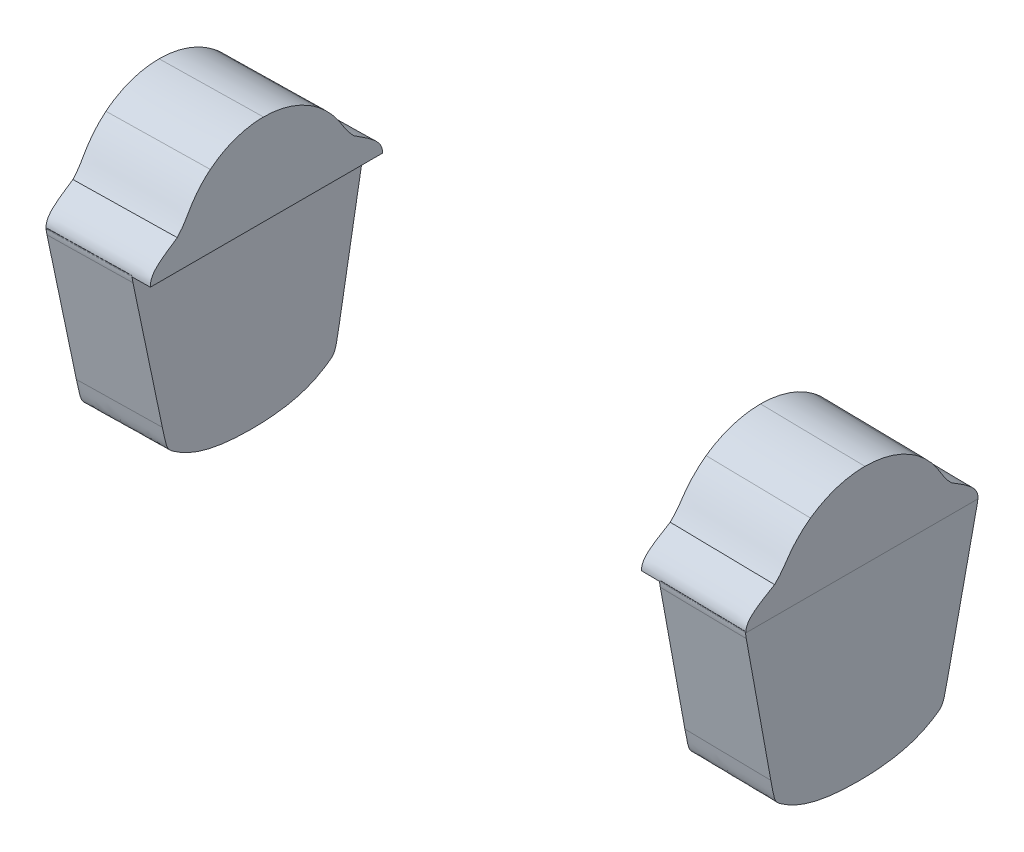
SolidWorks part; units mm, degrees
ref_plane "Front Plane" through (0, 0, 0) normal (0, 0, 1) x (1, 0, 0)
ref_plane "Top Plane" through (0, 0, 0) normal (0, 1, 0) x (1, 0, 0)
ref_plane "Right Plane" through (0, 0, 0) normal (1, 0, 0) x (0, 0, -1)
sketch "Sketch13" plane through (-330.9386, -5.7766, 0) normal (0.9998, 0.0175, 0) x (0, 0, -1)
  line L3 (82.505, 100.855) -> (104.453, 212.7636)
  line L4 (105.1118, 218.0433) -> (-84.0339, 218.0433)
  line L5 (-83.375, 212.7636) -> (-61.427, 100.855)
  line L6 (82.505, 100.855) -> (104.453, 212.7636)
  line L7 (105.1118, 218.0433) -> (-84.0339, 218.0433)
  line L8 (-83.375, 212.7636) -> (-61.427, 100.855)
  spline S6 degree 3 poles (7626.2022, 16335.3726) (93.3065, 1190.3174) (-262.8295, 156.049) (-31.4208, 69.2057) (-26.7523, 67.9017) (-16.9505, 65.8726) (-11.819, 65.149) (405.2965, 28.3291) (2318.1729, 1443.9996) (16961.578, -5460.1262) knots -12.504091 -12.504091 -12.504091 -12.504091 0.25 0.25 0.5 0.5 0.75 0.75 19.845941 19.845941 19.845941 19.845941 weights 1 1 1 1 1 1 1 1 1 1 only from (-48.4941, 77.0769) to (10.539, 63.9704)
  spline S7 degree 3 poles (-16940.096, -5459.9357) (-2297.0598, 1443.9736) (-384.2148, 28.3294) (32.8969, 65.149) (38.0285, 65.8726) (47.8302, 67.9017) (52.4988, 69.2057) (283.9075, 156.049) (-72.2286, 1190.3176) (-7605.1261, 16335.3764) knots -18.845765 -18.845765 -18.845765 -18.845765 0.25 0.25 0.5 0.5 0.75 0.75 13.504092 13.504092 13.504092 13.504092 weights 1 1 1 1 1 1 1 1 1 1 only from (10.539, 63.9704) to (69.5721, 77.0769)
  spline S8 degree 3 poles (-8963.5548, -15472.3763) (-752.2665, -318.1531) (7.9888, 36.6232) (73.8797, 79.8406) (74.6824, 80.3989) (76.0321, 81.4603) (76.5773, 81.961) (77.5011, 82.9989) (77.8915, 83.5469) (78.431, 84.5204) (78.6051, 84.8746) (78.9428, 85.6519) (79.1069, 86.0756) (79.5941, 87.4807) (79.9091, 88.59) (101.7921, 178.014) (164.8063, 1219.1751) (7787.4412, 16356.1941) knots -8.34761 -8.34761 -8.34761 -8.34761 0.125 0.125 0.25 0.25 0.375 0.375 0.5 0.5 0.5625 0.5625 0.625 0.625 0.75 0.75 9.036838 9.036838 9.036838 9.036838 weights 1 1 1 1 1 1 1 1 1 1 1 1 1 1 1 1 1 1 only from (69.5721, 77.0769) to (82.505, 100.855)
  spline S9 degree 3 poles (8221.7045, -15798.6868) (-629.2195, -357.5895) (98.26, 120.5911) (112.1266, 316.5514) (-660.8382, 12.0074) (-15219.7335, 9632.9671) knots -9.423347 -9.423347 -9.423347 -9.423347 0.125 0.125 10.033525 10.033525 10.033525 10.033525 weights 1 1 1 1 1 1 only from (104.453, 212.7636) to (105.1118, 218.0433)
  spline S10 degree 3 poles (15241.4841, 9633.4116) (681.9399, 11.998) (-91.0488, 316.5529) (-77.1822, 120.5925) (650.2762, -357.5756) (-8200.2406, -15798.0135) knots -9.86503 -9.86503 -9.86503 -9.86503 0.043648 0.043648 9.591856 9.591856 9.591856 9.591856 weights 1 1 1 1 1 1 only from (-84.0339, 218.0433) to (-83.375, 212.7636)
  spline S11 degree 3 poles (-7766.5357, 16356.5365) (-143.7293, 1219.1908) (-80.7143, 178.0147) (-58.8312, 88.59) (-58.5162, 87.4807) (-58.029, 86.0756) (-57.8649, 85.6519) (-57.5272, 84.8746) (-57.3531, 84.5204) (-56.8136, 83.5469) (-56.4232, 82.9989) (-55.4993, 81.961) (-54.9541, 81.4603) (-53.6044, 80.3989) (-52.8018, 79.8406) (13.0901, 36.6226) (773.3666, -318.1635) (8984.992, -15473.0393) knots -8.036901 -8.036901 -8.036901 -8.036901 0.25 0.25 0.375 0.375 0.4375 0.4375 0.5 0.5 0.625 0.625 0.75 0.75 0.875 0.875 9.347734 9.347734 9.347734 9.347734 weights 1 1 1 1 1 1 1 1 1 1 1 1 1 1 1 1 1 1 only from (-61.427, 100.855) to (-48.4941, 77.0769)
  spline S12 degree 3 poles (-48.4941, 77.0769) (-44.5431, 74.5789) (-40.3184, 72.5447) (-31.4208, 69.2057) (-26.7523, 67.9017) (-16.9505, 65.8726) (-11.819, 65.149) (-1.0385, 64.1973) (4.609, 63.9704) (10.539, 63.9704) knots 0 0 0 0 0.25 0.25 0.5 0.5 0.75 0.75 1 1 1 1 weights 1 1 1 1 1 1 1 1 1 1
  spline S13 degree 3 poles (10.539, 63.9704) (16.469, 63.9704) (22.1165, 64.1973) (32.8969, 65.149) (38.0285, 65.8726) (47.8302, 67.9017) (52.4988, 69.2057) (61.3963, 72.5447) (65.621, 74.5789) (69.5721, 77.0769) knots 0 0 0 0 0.25 0.25 0.5 0.5 0.75 0.75 1 1 1 1 weights 1 1 1 1 1 1 1 1 1 1
  spline S14 degree 3 poles (69.5721, 77.0769) (70.8544, 77.8877) (71.9638, 78.584) (73.8797, 79.8406) (74.6824, 80.3989) (76.0321, 81.4603) (76.5773, 81.961) (77.5011, 82.9989) (77.8915, 83.5469) (78.431, 84.5204) (78.6051, 84.8746) (78.9428, 85.6519) (79.1069, 86.0756) (79.5941, 87.4807) (79.9091, 88.59) (80.8846, 92.5765) (81.5727, 96.1016) (82.505, 100.855) knots 0 0 0 0 0.125 0.125 0.25 0.25 0.375 0.375 0.5 0.5 0.5625 0.5625 0.625 0.625 0.75 0.75 1 1 1 1 weights 1 1 1 1 1 1 1 1 1 1 1 1 1 1 1 1 1 1
  spline S15 degree 3 poles (104.453, 212.7636) (104.7645, 214.1816) (104.9761, 215.5021) (105.0958, 217.1935) (105.1118, 217.6218) (105.1118, 218.0433) knots 0.000354 0.000354 0.000354 0.000354 0.125 0.125 0.168294 0.168294 0.168294 0.168294 weights 1 1 1 1 1 1
  spline S16 degree 3 poles (-84.0339, 218.0433) (-84.0339, 217.6218) (-84.0179, 217.1935) (-83.8982, 215.5021) (-83.6866, 214.1816) (-83.375, 212.7636) knots 0.000354 0.000354 0.000354 0.000354 0.043648 0.043648 0.168294 0.168294 0.168294 0.168294 weights 1 1 1 1 1 1
  spline S17 degree 3 poles (-61.427, 100.855) (-60.4948, 96.1016) (-59.8067, 92.5765) (-58.8312, 88.59) (-58.5162, 87.4807) (-58.029, 86.0756) (-57.8649, 85.6519) (-57.5272, 84.8746) (-57.3531, 84.5204) (-56.8136, 83.5469) (-56.4232, 82.9989) (-55.4993, 81.961) (-54.9541, 81.4603) (-53.6044, 80.3989) (-52.8018, 79.8406) (-50.8858, 78.584) (-49.7765, 77.8877) (-48.4941, 77.0769) knots 0 0 0 0 0.25 0.25 0.375 0.375 0.4375 0.4375 0.5 0.5 0.625 0.625 0.75 0.75 0.875 0.875 1 1 1 1 weights 1 1 1 1 1 1 1 1 1 1 1 1 1 1 1 1 1 1
  dimension "D1" = 0
extrude "Boss-Extrude1" add sketch "Sketch13" along normal blind 70 from offset 50 separate body
sketch "Sketch14" plane through (-277.0872, -9.6761, 0) normal (0.9994, 0.0349, 0) x (0, 0, -1)
  line L1 (-84.0231, 222.0431) -> (105.1011, 222.0431)
  line L2 (-84.0231, 222.0431) -> (105.1011, 222.0431)
  spline S6 degree 2 poles (5382.3297, -4104.2021) (311.5748, 636.7455) (-41.4346, 271.4203) (-45.2753, 267.4456) (-48.46, 262.9662) (-49.2003, 261.9249) (-50.0127, 260.7006) (-50.6823, 259.6915) (-51.5083, 258.3944) (-51.7922, 257.9484) (-52.2439, 257.2325) (-52.8322, 256.3001) (-52.9781, 256.0697) (-53.8513, 254.6905) (-54.4673, 253.7605) (-56.096, 251.3012) (-57.6776, 249.3237) (-297.7474, -50.8443) (-6935.3487, 1483.9527) knots -22.859625 -22.859625 -22.859625 0.25 0.25 0.5 0.5 0.5625 0.5625 0.625 0.625 0.65625 0.65625 0.6875 0.6875 0.75 0.75 0.875 0.875 18.832979 18.832979 18.832979 only from (-33.2448, 278.7269) to (-61.3296, 245.2339)
  spline S7 degree 2 poles (5930.5505, 3863.7565) (57.6161, 320.2206) (-64.9183, 242.9931) (-66.8739, 241.7606) (-68.4807, 240.7123) (-70.427, 239.4425) (-71.9939, 238.3559) (-73.913, 237.0251) (-75.4132, 235.8649) (-77.2608, 234.4361) (-78.6285, 233.1445) (-80.3322, 231.5357) (-81.4458, 229.989) (-82.0893, 229.095) (-82.5638, 228.1868) (-83.064, 227.2294) (-83.3895, 226.2273) (-146.1003, 33.1712) (5997.7888, -3233.0606) knots -10.71994 -10.71994 -10.71994 0.125 0.125 0.25 0.25 0.375 0.375 0.5 0.5 0.625 0.625 0.75 0.75 0.8125 0.8125 0.875 0.875 13.331152 13.331152 13.331152 only from (-61.3296, 245.2339) to (-84.0231, 222.0431)
  spline S8 degree 3 poles (7099.4552, 417.9562) (33.7422, 171.0257) (106.9497, 198.6055) (105.0313, 223.5586) (104.9316, 224.3311) (104.7815, 225.1141) (104.5764, 225.9071) (104.3103, 226.7096) (103.9775, 227.5213) (103.5717, 228.3417) (103.0877, 229.1717) (102.1684, 230.5333) (100.7506, 232.177) (98.9584, 233.8577) (97.5515, 235.0337) (96.1206, 236.1607) (94.4601, 237.3912) (92.307, 238.8932) (90.0075, 240.4269) (87.5759, 241.9971) (-20.5227, 310.2792) (-159.6048, 327.1069) (3459.6832, 6362.2993) knots -2.147809 -2.147809 -2.147809 -2.147809 0.022137 0.044649 0.067605 0.091096 0.115221 0.140113 0.165931 0.19286 0.221122 0.250979 0.338288 0.412598 0.468467 0.500662 0.573936 0.651492 0.733183 0.818756 0.907882 12.058636 12.058636 12.058636 12.058636 only from (105.1011, 222.0431) to (82.4076, 245.2339)
  spline S9 degree 2 poles (6949.7745, 1520.3026) (319.1368, -51.545) (78.7391, 249.3443) (77.1571, 251.3243) (75.524, 253.7924) (74.9106, 254.7196) (74.0342, 256.1042) (73.9122, 256.2968) (73.2996, 257.2677) (72.8512, 257.9784) (72.5634, 258.4301) (71.739, 259.7242) (71.0667, 260.7366) (70.255, 261.9588) (69.5138, 263.0001) (66.3354, 267.4654) (62.5032, 271.43) (-290.4737, 636.5993) (-5366.1752, -4097.8963) knots -17.777878 -17.777878 -17.777878 0.125 0.125 0.25 0.25 0.3125 0.3125 0.34375 0.34375 0.375 0.375 0.4375 0.4375 0.5 0.5 0.75 0.75 23.884006 23.884006 23.884006 only from (82.4076, 245.2339) to (54.3227, 278.7269)
  spline S10 degree 2 poles (-2853.7492, -6053.0352) (487.207, 48.5223) (44.4463, 285.0914) (39.269, 287.8577) (33.7108, 289.7485) (28.0965, 291.6584) (22.2443, 292.6234) (-472.9189, 374.2734) (-1541.3, -6498.9729) knots -21.04042 -21.04042 -21.04042 0.25 0.25 0.5 0.5 0.75 0.75 22.044828 22.044828 22.044828 only from (54.3227, 278.7269) to (10.539, 293.5819)
  spline S11 degree 2 poles (1556.2138, -6500.3892) (494.0546, 374.4836) (-1.1955, 292.6186) (-6.9806, 291.6623) (-12.5356, 289.7815) (-18.1355, 287.8855) (-23.3518, 285.1002) (-466.0866, 48.7017) (2866.6192, -6056.7568) knots -20.994538 -20.994538 -20.994538 0.25 0.25 0.5 0.5 0.75 0.75 22.004045 22.004045 22.004045 only from (10.539, 293.5819) to (-33.2448, 278.7269)
  spline S12 degree 2 poles (-33.2448, 278.7269) (-37.6158, 275.3724) (-41.4346, 271.4203) (-45.2753, 267.4456) (-48.46, 262.9662) (-49.2003, 261.9249) (-50.0127, 260.7006) (-50.6823, 259.6915) (-51.5083, 258.3944) (-51.7922, 257.9484) (-52.2439, 257.2325) (-52.8322, 256.3001) (-52.9781, 256.0697) (-53.8513, 254.6905) (-54.4673, 253.7605) (-56.096, 251.3012) (-57.6776, 249.3237) (-59.3486, 247.2344) (-61.3296, 245.2339) knots 0 0 0 0.25 0.25 0.5 0.5 0.5625 0.5625 0.625 0.625 0.65625 0.65625 0.6875 0.6875 0.75 0.75 0.875 0.875 1 1 1
  spline S13 degree 2 poles (-61.3296, 245.2339) (-63.5059, 243.8832) (-64.9183, 242.9931) (-66.8739, 241.7606) (-68.4807, 240.7123) (-70.427, 239.4425) (-71.9939, 238.3559) (-73.913, 237.0251) (-75.4132, 235.8649) (-77.2608, 234.4361) (-78.6285, 233.1445) (-80.3322, 231.5357) (-81.4458, 229.989) (-82.0893, 229.095) (-82.5638, 228.1868) (-83.064, 227.2294) (-83.3895, 226.2273) (-84.0188, 224.29) (-84.0231, 222.0431) knots 0 0 0 0.125 0.125 0.25 0.25 0.375 0.375 0.5 0.5 0.625 0.625 0.75 0.75 0.8125 0.8125 0.875 0.875 1 1 1
  spline S14 degree 3 poles (105.1011, 222.0431) (105.0973, 222.293) (105.0898, 222.7971) (105.0313, 223.5586) (104.9316, 224.3311) (104.7815, 225.1141) (104.5764, 225.9071) (104.3103, 226.7096) (103.9775, 227.5213) (103.5717, 228.3417) (103.0877, 229.1717) (102.1684, 230.5333) (100.7506, 232.177) (98.9584, 233.8577) (97.5515, 235.0337) (96.1206, 236.1607) (94.4601, 237.3912) (92.307, 238.8932) (90.0075, 240.4269) (87.5759, 241.9971) (85.0292, 243.6057) (83.291, 244.6852) (82.4076, 245.2339) knots 0 0 0 0 0.022137 0.044649 0.067605 0.091096 0.115221 0.140113 0.165931 0.19286 0.221122 0.250979 0.338288 0.412598 0.468467 0.500662 0.573936 0.651492 0.733183 0.818756 0.907882 1 1 1 1
  spline S15 degree 2 poles (82.4076, 245.2339) (80.4175, 247.2434) (78.7391, 249.3443) (77.1571, 251.3243) (75.524, 253.7924) (74.9106, 254.7196) (74.0342, 256.1042) (73.9122, 256.2968) (73.2996, 257.2677) (72.8512, 257.9784) (72.5634, 258.4301) (71.739, 259.7242) (71.0667, 260.7366) (70.255, 261.9588) (69.5138, 263.0001) (66.3354, 267.4654) (62.5032, 271.43) (58.6887, 275.3762) (54.3227, 278.7269) knots 0 0 0 0.125 0.125 0.25 0.25 0.3125 0.3125 0.34375 0.34375 0.375 0.375 0.4375 0.4375 0.5 0.5 0.75 0.75 1 1 1
  spline S16 degree 2 poles (54.3227, 278.7269) (49.6454, 282.3135) (44.4463, 285.0914) (39.269, 287.8577) (33.7108, 289.7485) (28.0965, 291.6584) (22.2443, 292.6234) (16.4312, 293.5819) (10.539, 293.5819) knots 0 0 0 0.25 0.25 0.5 0.5 0.75 0.75 1 1 1
  spline S17 degree 2 poles (10.539, 293.5819) (4.6325, 293.5819) (-1.1955, 292.6186) (-6.9806, 291.6623) (-12.5356, 289.7815) (-18.1355, 287.8855) (-23.3518, 285.1002) (-28.5595, 282.3196) (-33.2448, 278.7269) knots 0 0 0 0.25 0.25 0.5 0.5 0.75 0.75 1 1 1
  dimension "D1" = 0
extrude "Boss-Extrude2" add sketch "Sketch14" along direction (0.9998, 0.0175, 0) on the side of the normal blind 85 separate body
mirror "Mirror5" about plane through (0, 0, 0) normal (1, 0, 0) of bodies 359 361
ref_point "Point1"
ref_axis "Axis1" through (213.5404, 144.3299, -10.5399) along (-0.9998, 0.0175, 0)
ref_point "Point2"
ref_point "Point3"
